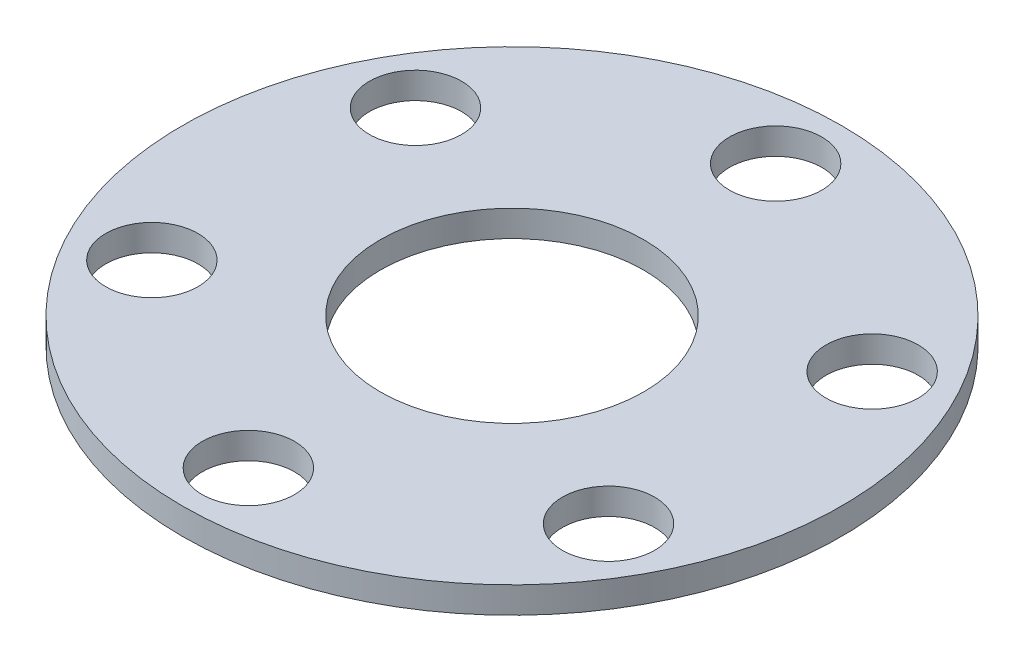
SolidWorks part; units mm, degrees
material "Stainless Steel (ferritic)"
ref_plane "Front Plane" through (0, 0, 0) normal (0, 0, 1) x (1, 0, 0)
ref_plane "Top Plane" through (0, 0, 0) normal (0, 1, 0) x (1, 0, 0)
ref_plane "Right Plane" through (0, 0, 0) normal (1, 0, 0) x (0, 0, -1)
sketch "Sketch1" plane through (0, 0, 0) normal (0, 1, 0) x (1, 0, 0)
  circle A0 centre (0, 0) radius 10 construction
  circle A1 centre (0, 0) radius 12.5
  circle A2 centre (0, 0) radius 5
  dimension "D1" = 20
  dimension "D3" = 25
  dimension "D2" = 5
extrude "Boss-Extrude1" add sketch "Sketch1" along normal blind 1
sketch "Sketch2" plane through (0, 0, 0) normal (0, 1, 0) x (1, 0, 0)
  circle A0 centre (0, 0) radius 10 construction
  circle A1 centre (0, 10) radius 1.75
  dimension "D1" = 3.5
  dimension "D2" = 20
extrude "Cut-Extrude1" cut sketch "Sketch2" along normal through all
pattern_circular "CirPattern1" count 6 over 360 about axis through (0, 1, 0) along (0, 1, 0) of "Cut-Extrude1"
equation "\"motor_shaft_mounting_hole_circle_diameter\"= 20mm"
equation "\"ring_width\"= 10mm"
equation "\"material_thickness\"= 1mm"
equation "\"D1@Sketch1\"=\"motor_shaft_mounting_hole_circle_diameter\""
equation "\"D2@Sketch1\"=\"ring_width\"/2"
equation "\"D1@Boss-Extrude1\"=\"material_thickness\""
equation "\"D2@Sketch2\"=\"motor_shaft_mounting_hole_circle_diameter\""
